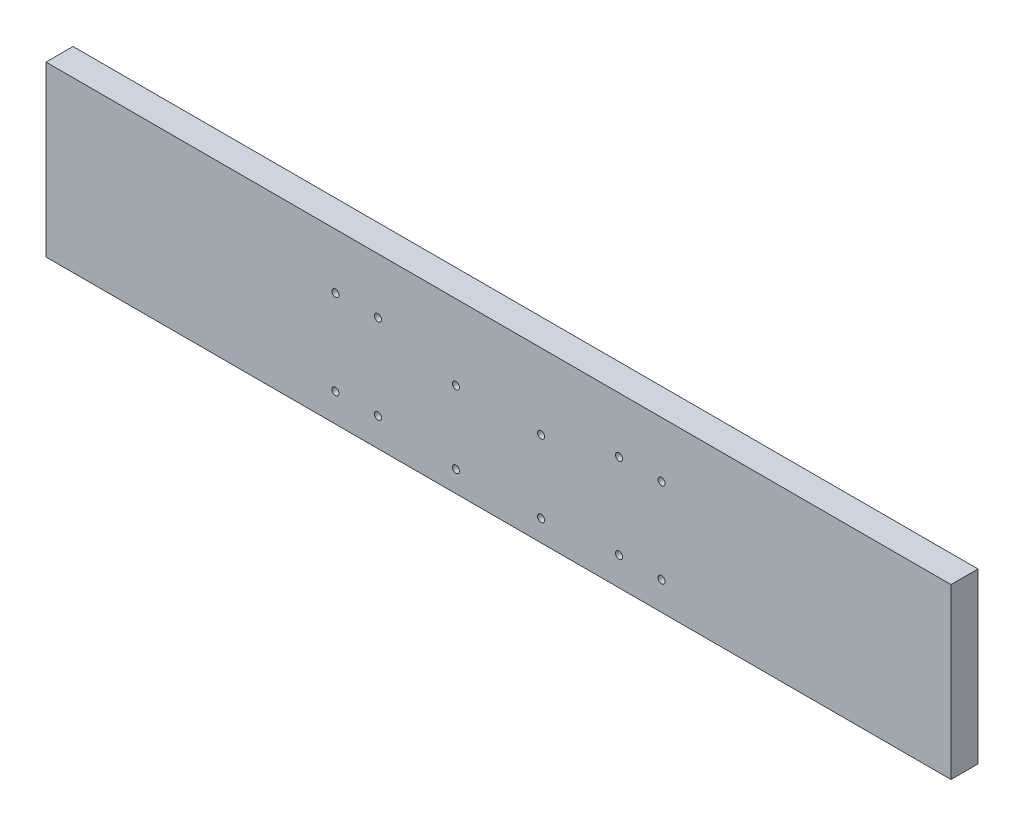
SolidWorks part; units mm, degrees
ref_plane "Front Plane" through (0, 0, 0) normal (0, 0, 1) x (1, 0, 0)
ref_plane "Top Plane" through (0, 0, 0) normal (0, 1, 0) x (1, 0, 0)
ref_plane "Right Plane" through (0, 0, 0) normal (1, 0, 0) x (0, 0, -1)
sketch "Sketch1" plane through (0, 0, 0) normal (0, 0, 1) x (1, 0, 0)
  line L1 (0, 119.05) -> (-638.1, 119.05)
  line L2 (0, 119.05) -> (0, 0)
  line L3 (0, 0) -> (-638.1, 0)
  line L4 (-638.1, 119.05) -> (-638.1, 0)
  dimension "D1" = 119.05
  dimension "D2" = 638.1
extrude "Boss-Extrude1" add sketch "Sketch1" along normal blind 19.05
hole_wizard "Ø5.0mm Dowel Hole1" positions "Sketch2" profile "Sketch3" hole size "Ø5.0" standard "ANSI Metric"
sketch "Sketch2" plane through (0, 0, 0) normal (0, 0, -1) x (-1, 0, 0)
  point P0 (434.05, 20)
  point P3 (404.05, 20)
  point P6 (404.05, 80)
  point P9 (434.05, 80)
  point P12 (349.05, 15)
  point P15 (349.05, 66)
  point P18 (289.05, 66)
  point P25 (289.05, 15)
  point P28 (234.05, 20)
  point P31 (234.05, 80)
  point P34 (204.05, 80)
  point P37 (204.05, 20)
sketch "Sketch3" plane through (-434.05, 20, 0) normal (1, 0, 0) x (0, 1, 0)
  line L0 (0, 0) -> (0, 30)
  line L1 (0, 30) -> (2.5, 28.4978)
  line L2 (2.5, 28.4978) -> (2.5, 0)
  line L5 (2.5, 0) -> (0, 0)
  line L10 (0, 30) -> (-2.5, 28.4978) construction
  line L11 (0, -6.35) -> (0, 107.95) construction
  dimension "Hole Dia." = 5
  dimension "Hole Depth" = 30
  dimension "Drill Angle" = 118
